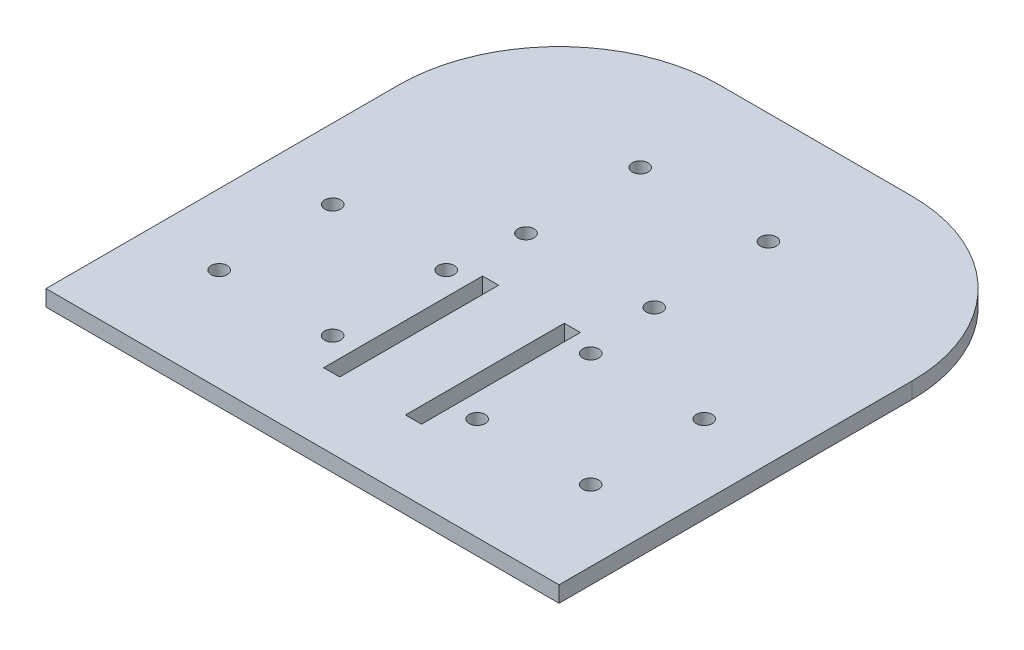
SolidWorks part; units mm, degrees
material "Acrylic (Medium-high impact)"
ref_plane "Front Plane" through (0, 0, 0) normal (0, 0, 1) x (1, 0, 0)
ref_plane "Top Plane" through (0, 0, 0) normal (0, 1, 0) x (1, 0, 0)
ref_plane "Right Plane" through (0, 0, 0) normal (1, 0, 0) x (0, 0, -1)
sketch "Sketch1" plane through (0, 0, 0) normal (0, 1, 0) x (1, 0, 0)
  line L1 (-101.6, -101.6) -> (101.6, -101.6)
  line L2 (-101.6, -101.6) -> (-101.6, 101.6)
  line L3 (-101.6, 101.6) -> (101.6, 101.6)
  line L4 (101.6, -101.6) -> (101.6, 101.6)
  line L5 (-101.6, -101.6) -> (101.6, 101.6) construction
  line L6 (-101.6, 101.6) -> (101.6, -101.6) construction
  point P0 (0, 0)
  dimension "D1" = 203.2
  dimension "D2" = 203.2
extrude "Boss-Extrude1" add sketch "Sketch1" along normal blind 6.35
sketch "Sketch2" plane through (0, 6.35, 0) normal (0, 1, 0) x (1, 0, 0)
  line L9 (101.6, 38.1) -> (101.6, 101.6)
  line L10 (101.6, 101.6) -> (38.1, 101.6)
  line L11 (-38.1, 101.6) -> (-101.6, 101.6)
  line L12 (-101.6, 101.6) -> (-101.6, 38.1)
  arc A2 (101.6, 38.1) -> (38.1, 101.6) centre (38.1, 38.1) ccw
  arc A3 (-101.6, 38.1) -> (-38.1, 101.6) centre (-38.1, 38.1) cw
extrude "Cut-Extrude1" cut sketch "Sketch2" against normal through all
sketch "Sketch9" plane through (0, 0, 0) normal (0, -1, 0) x (1, 0, 0)
  line L0 (-38.766, 10.8317) -> (-38.512, 10.8317) construction
  line L1 (-38.766, 73.756) -> (-38.512, 73.756) construction
  line L2 (38.5855, 10.8317) -> (38.3315, 10.8317) construction
  line L3 (-38.512, 10.8317) -> (-32.162, 10.8317)
  line L4 (-38.512, 10.8317) -> (-38.512, 73.756)
  line L5 (-38.512, 73.756) -> (-32.162, 73.756)
  line L6 (-32.162, 10.8317) -> (-32.162, 73.756)
  line L7 (38.5855, 73.756) -> (38.3315, 73.756) construction
  line L8 (-101.6, 101.6) -> (101.6, 101.6) construction
  line L13 (38.3315, 73.756) -> (31.9815, 73.756)
  line L14 (38.3315, 73.756) -> (38.3315, 10.8317)
  line L15 (38.3315, 10.8317) -> (31.9815, 10.8317)
  line L16 (31.9815, 73.756) -> (31.9815, 10.8317)
  line L17 (-101.6, -38.1) -> (-101.6, 101.6) construction
  circle A0 centre (-47.7463, 64.7757) radius 3.175 construction
  circle A1 centre (-47.7463, 19.812) radius 3.175 construction
  circle A2 centre (-92.71, 19.812) radius 3.175 construction
  circle A3 centre (-92.71, 64.7757) radius 3.175 construction
  circle A4 centre (-25.4903, -11.842) radius 3.175 construction
  circle A5 centre (25.3097, -11.842) radius 3.175 construction
  circle A6 centre (25.3097, -57.054) radius 3.175 construction
  circle A7 centre (-25.4903, -57.054) radius 3.175 construction
  circle A8 centre (47.5658, 19.812) radius 3.175 construction
  circle A9 centre (92.5295, 19.812) radius 3.175 construction
  circle A10 centre (92.5295, 64.7757) radius 3.175 construction
  circle A11 centre (47.5658, 64.7757) radius 3.175 construction
  circle A12 centre (-25.4903, -31.4508) radius 3.175
  circle A13 centre (25.3097, -31.4508) radius 3.175
  circle A14 centre (-25.4903, -76.6628) radius 3.175
  circle A15 centre (25.3097, -76.6628) radius 3.175
  circle A16 centre (-47.7463, 80.0157) radius 3.175
  circle A17 centre (-92.71, 80.0157) radius 3.175
  circle A18 centre (-47.7463, 35.052) radius 3.16
  circle A19 centre (-92.71, 35.052) radius 3.2058
  circle A20 centre (47.5658, 80.0157) radius 3.175
  circle A21 centre (92.5295, 80.0157) radius 3.175
  circle A22 centre (47.5658, 35.052) radius 3.175
  circle A23 centre (92.5295, 35.052) radius 3.175
  dimension "D22" = 6.35
  dimension "D23" = 6.35
  dimension "D24" = 6.35
  dimension "D26" = 6.35
  dimension "D27" = 6.35
  dimension "D28" = 6.35
  dimension "D29" = 6.35
  dimension "D30" = 6.35
  dimension "D31" = 6.35
  dimension "D32" = 6.35
  dimension "D33" = 6.35
  dimension "D36" = 19.6088
  dimension "D37" = 19.6088
  dimension "D38" = 19.6088
  dimension "D40" = 15.24
  dimension "D41" = 15.24
  dimension "D44" = 6.35
  dimension "D45" = 6.35
  dimension "D46" = 6.35
  dimension "D47" = 6.35
  dimension "D48" = 6.35
  dimension "D49" = 6.35
  dimension "D50" = 6.4115
  dimension "D51" = 6.32
  dimension "D1" = 0.254
  dimension "D2" = 6.35
  dimension "D4" = 44.9637
  dimension "D5" = 63.5883
  dimension "D6" = 44.9637
  dimension "D7" = 54.6863
  dimension "D8" = 53.944
  dimension "D9" = 60.548
  dimension "D10" = 135.86
  dimension "D11" = 141.9453
  dimension "D12" = 125.0145
  dimension "D13" = 131.2955
  dimension "D14" = 140.2758
  dimension "D15" = 185.2395
  dimension "D16" = 190.6185
  dimension "D17" = 122.191
  dimension "D18" = 74.2999
  dimension "D19" = 102.1121
  dimension "D20" = 140.8441
  dimension "D21" = 3.175
  dimension "D25" = 147.3059
  dimension "D34" = 8.89
  dimension "D35" = 81.788
  dimension "D39" = 19.6088
  dimension "D42" = 15.24
  dimension "D43" = 15.24
  dimension "D52" = 15.24
  dimension "D53" = 15.24
  dimension "D54" = 15.24
  dimension "D55" = 15.24
extrude "Cut-Extrude2" [suppressed] cut sketch "Sketch9" against normal through all
sketch "Sketch10" plane through (0, 0, 0) normal (0, -1, 0) x (1, 0, 0)
  line L0 (-19.462, 10.8317) -> (-13.112, 10.8317)
  line L1 (-13.112, 10.8317) -> (-13.112, 73.756)
  line L2 (-13.112, 73.756) -> (-19.462, 73.756)
  line L3 (-19.462, 73.756) -> (-19.462, 10.8317)
  line L4 (-38.512, 10.8317) -> (-32.162, 10.8317)
  line L5 (-32.162, 10.8317) -> (-32.162, 73.756)
  line L6 (-32.162, 73.756) -> (-38.512, 73.756)
  line L7 (-38.512, 73.756) -> (-38.512, 10.8317)
  line L8 (-38.512, 10.8317) -> (-32.162, 10.8317) construction
  line L9 (-32.162, 10.8317) -> (-32.162, 73.756) construction
  line L10 (-32.162, 73.756) -> (-38.512, 73.756) construction
  line L11 (-38.512, 73.756) -> (-38.512, 10.8317) construction
  line L12 (38.3315, 73.756) -> (31.9815, 73.756)
  line L13 (31.9815, 73.756) -> (31.9815, 10.8317)
  line L14 (31.9815, 10.8317) -> (38.3315, 10.8317)
  line L15 (38.3315, 10.8317) -> (38.3315, 73.756)
  line L16 (38.3315, 73.756) -> (31.9815, 73.756) construction
  line L17 (31.9815, 73.756) -> (31.9815, 10.8317) construction
  line L18 (31.9815, 10.8317) -> (38.3315, 10.8317) construction
  line L19 (38.3315, 10.8317) -> (38.3315, 73.756) construction
  line L20 (12.9315, 73.756) -> (19.2815, 73.756)
  line L21 (19.2815, 73.756) -> (19.2815, 10.8317)
  line L22 (19.2815, 10.8317) -> (12.9315, 10.8317)
  line L23 (12.9315, 10.8317) -> (12.9315, 73.756)
  circle A1 centre (25.3097, -31.4508) radius 3.175
  circle A2 centre (25.3097, -31.4508) radius 3.175 construction
  circle A3 centre (-25.4903, -31.4508) radius 3.175
  circle A4 centre (-25.4903, -31.4508) radius 3.175 construction
  circle A5 centre (25.3097, -76.6628) radius 3.175
  circle A6 centre (25.3097, -76.6628) radius 3.175 construction
  circle A7 centre (-25.4903, -76.6628) radius 3.175
  circle A8 centre (-25.4903, -76.6628) radius 3.175 construction
  circle A9 centre (-92.71, 80.0157) radius 3.175
  circle A10 centre (-92.71, 80.0157) radius 3.175 construction
  circle A11 centre (-47.7463, 80.0157) radius 3.175
  circle A12 centre (-47.7463, 80.0157) radius 3.175 construction
  circle A13 centre (92.5295, 35.052) radius 3.175
  circle A14 centre (92.5295, 35.052) radius 3.175 construction
  circle A15 centre (47.5658, 35.052) radius 3.175
  circle A16 centre (47.5658, 35.052) radius 3.175 construction
  circle A17 centre (92.5295, 80.0157) radius 3.175
  circle A18 centre (92.5295, 80.0157) radius 3.175 construction
  circle A19 centre (47.5658, 80.0157) radius 3.175
  circle A20 centre (47.5658, 80.0157) radius 3.175 construction
  circle A21 centre (-92.71, 35.052) radius 3.2058
  circle A22 centre (-92.71, 35.052) radius 3.2058 construction
  circle A23 centre (-47.7463, 35.052) radius 3.16
  circle A24 centre (-47.7463, 35.052) radius 3.16 construction
  circle A25 centre (-73.66, 80.0157) radius 3.175 construction
  circle A26 centre (-28.6963, 80.0157) radius 3.175 construction
  circle A27 centre (-73.66, 35.052) radius 3.175 construction
  circle A28 centre (-28.6963, 35.052) radius 3.175 construction
  circle A29 centre (28.5158, 80.0157) radius 3.175 construction
  circle A30 centre (73.4795, 80.0157) radius 3.175 construction
  circle A31 centre (73.4795, 35.052) radius 3.175 construction
  circle A32 centre (28.5158, 35.052) radius 3.175 construction
  circle A33 centre (25.3097, -12.4008) radius 3.175
  circle A34 centre (-25.4903, -12.4008) radius 3.175
  circle A35 centre (-25.4903, -57.6128) radius 3.175
  circle A36 centre (25.3097, -57.6128) radius 3.175
  circle A37 centre (-73.66, 16.002) radius 3.175
  circle A38 centre (-73.66, 60.9657) radius 3.175
  circle A39 centre (-28.6963, 60.9657) radius 3.175
  circle A40 centre (-28.6963, 16.002) radius 3.175
  circle A41 centre (28.5158, 60.9657) radius 3.175
  circle A42 centre (73.4795, 60.9657) radius 3.175
  circle A43 centre (73.4795, 16.002) radius 3.175
  circle A44 centre (28.5158, 16.002) radius 3.175
  dimension "D17" = 6.35
  dimension "D19" = 6.35
  dimension "D21" = 6.35
  dimension "D24" = 6.35
  dimension "D25" = 6.35
  dimension "D26" = 6.35
  dimension "D27" = 6.35
  dimension "D28" = 6.35
  dimension "D29" = 6.35
  dimension "D30" = 6.35
  dimension "D31" = 6.35
  dimension "D32" = 6.35
  dimension "D41" = 6.35
  dimension "D42" = 6.35
  dimension "D43" = 6.35
  dimension "D44" = 6.35
  dimension "D50" = 6.35
  dimension "D53" = 6.35
  dimension "D54" = 6.35
  dimension "D57" = 6.35
  dimension "D15" = 25.4
  dimension "D16" = 25.4
  dimension "D18" = 19.05
  dimension "D20" = 19.05
  dimension "D22" = 19.05
  dimension "D23" = 19.05
  dimension "D33" = 19.05
  dimension "D34" = 19.05
  dimension "D35" = 19.05
  dimension "D36" = 19.05
  dimension "D37" = 19.05
  dimension "D38" = 19.05
  dimension "D39" = 19.05
  dimension "D40" = 19.05
  dimension "D45" = 19.05
  dimension "D46" = 19.05
  dimension "D47" = 0
  dimension "D48" = 19.05
  dimension "D49" = 19.05
  dimension "D51" = 19.05
  dimension "D52" = 19.05
  dimension "D55" = 19.05
  dimension "D56" = 19.05
  dimension "D1" = 0
  dimension "D2" = 0
  dimension "D3" = 0
  dimension "D4" = 0
  dimension "D5" = 0
  dimension "D6" = 0
  dimension "D7" = 0
  dimension "D8" = 0
  dimension "D9" = 0
  dimension "D10" = 0
  dimension "D11" = 0
  dimension "D12" = 0
  dimension "D13" = 0
  dimension "D14" = 0
extrude "Cut-Extrude4" cut sketch "Sketch10" against normal through all
sketch "Sketch11" plane through (0, 0, 0) normal (0, -1, 0) x (1, 0, 0)
  line L0 (0, -101.6) -> (0, 101.6) construction
  line L1 (38.1, -101.6) -> (-38.1, -101.6) construction
  line L2 (-101.6, 101.6) -> (101.6, 101.6) construction
  line L3 (0, 0) -> (-33.8896, 19.5662) construction
  line L4 (0, 0) -> (55.2542, 31.901) construction
  line L18 (-73.66, 60.9657) -> (-28.6963, 60.9657)
  line L19 (-73.66, 60.9657) -> (-73.66, 16.002)
  line L20 (-73.66, 16.002) -> (-28.6963, 16.002)
  line L21 (-28.6963, 60.9657) -> (-28.6963, 16.002)
  line L22 (28.5158, 60.9657) -> (73.4795, 60.9657)
  line L23 (28.5158, 60.9657) -> (28.5158, 16.002)
  line L24 (28.5158, 16.002) -> (73.4795, 16.002)
  line L25 (73.4795, 60.9657) -> (73.4795, 16.002)
  dimension "D3" = 60
  dimension "D1" = 0
  dimension "D2" = 0
  dimension "D4" = 30
  dimension "D5" = 60
  dimension "D6" = 30
